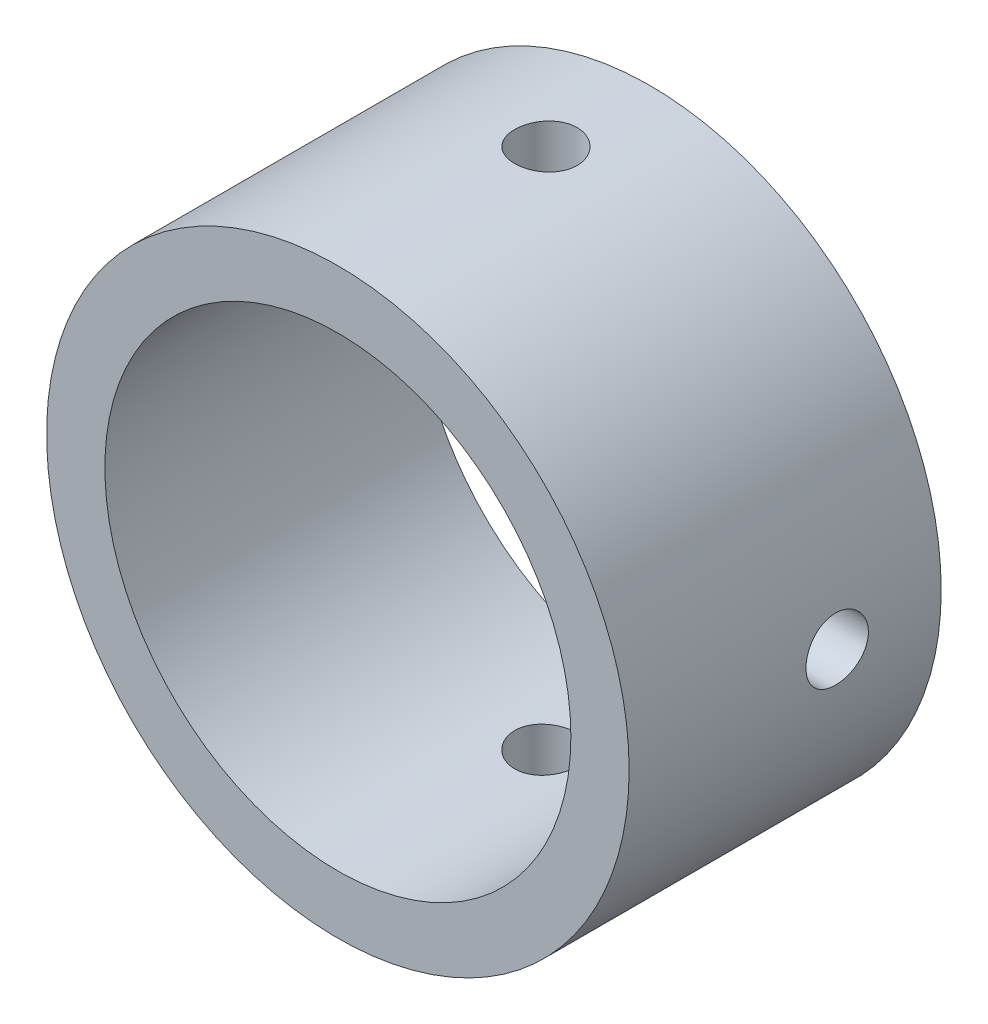
SolidWorks part; units mm, degrees
ref_plane "Front Plane" through (0, 0, 0) normal (0, 0, 1) x (1, 0, 0)
ref_plane "Top Plane" through (0, 0, 0) normal (0, 1, 0) x (1, 0, 0)
ref_plane "Right Plane" through (0, 0, 0) normal (1, 0, 0) x (0, 0, -1)
ref_axis "Z" through (0, 0, 10.75) along (0, 0, -1)
ref_axis "X" through (17.0818, 0, 0) along (-1, 0, 0)
ref_axis "Y" through (0, 15.4, 0) along (0, -1, 0)
sketch "Sketch1" plane through (0, 0, 0) normal (0, 0, 1) x (1, 0, 0)
  circle A0 centre (0, 0) radius 14
  circle A1 centre (0, 0) radius 11.2
  dimension "D1" = 28
  dimension "D2" = 22.4
extrude "Boss-Extrude1" add sketch "Sketch1" against normal blind 5 and the other way blind 10
sketch "Sketch2" plane through (0, 0, 0) normal (0, 1, 0) x (1, 0, 0)
  line L0 (-15.4, 0) -> (15.4, 0) construction
  line L1 (0, -8.25) -> (0, 8.25) construction
  circle A0 centre (0, 0) radius 1.5
  dimension "D1" = 3
extrude "Cut-Extrude1" cut sketch "Sketch2" against normal through all both and the other way through all
sketch "Sketch3" plane through (0, 0, 0) normal (1, 0, 0) x (0, 0, -1)
  circle A0 centre (0, 0) radius 1.5
  dimension "D1" = 3
extrude "Cut-Extrude2" cut sketch "Sketch3" along normal through all
equation "\"EyeDiameter\" = 28"
equation "\"BasePlaneDistance\" = 45"
equation "\"EyeClearance\" = 2"
equation "\"EyeOD\"= \"EyeDiameter\""
equation "\"D1@Sketch1\"=\"EyeOD\""
equation "\"D2@Sketch1\"=\"EyeDiameter\"*0.8"
equation "\"pinHoleDiameter\"= 3"
equation "\"D1@Sketch2\"=\"pinHoleDiameter\""
equation "\"D1@Sketch3\"=\"pinHoleDiameter\""
